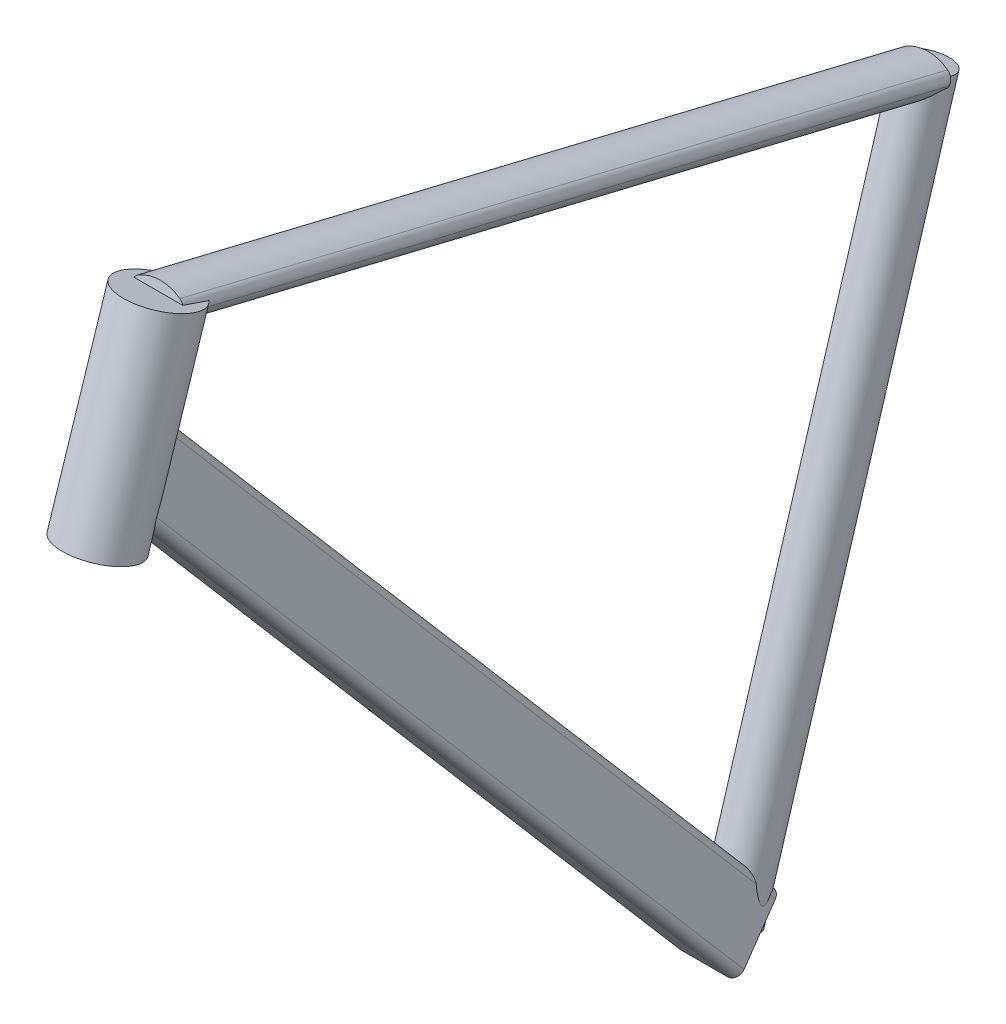
SolidWorks part; units mm, degrees
ref_plane "Plan de face" through (0, 0, 0) normal (0, 0, 1) x (1, 0, 0)
ref_plane "Plan de dessus" through (0, 0, 0) normal (0, 1, 0) x (1, 0, 0)
ref_plane "Plan de droite" through (0, 0, 0) normal (1, 0, 0) x (0, 0, -1)
sketch "Esquisse1" plane through (0, 0, 0) normal (1, 0, 0) x (0, 0, -1)
  line L0 (0, 0) -> (-416.4955, 485.9336)
  line L4 (-416.4955, 485.9336) -> (-390.3242, 566.9614)
  line L5 (-390.3242, 566.9614) -> (132.9546, 440.367)
  line L6 (132.9546, 440.367) -> (0, 0)
  line L7 (-390.3242, 566.9614) -> (220.5054, 566.9614) construction
  line L8 (0, 0) -> (154.0318, 132.0212) construction
  line L9 (-416.4955, 485.9336) -> (-477.5022, 505.6383) construction
  line L10 (0, 0) -> (73.466, -22.1807) construction
  line L11 (-390.3242, 566.9614) -> (-377.98, 617.9864) construction
  point P0 (0, 0)
  dimension "D1" = 13.6
  dimension "D2" = 35.8
  dimension "D3" = 640
  dimension "D4" = 86.8
  dimension "D5" = 94.3
  dimension "D6" = 460
ref_plane "Plan1" through (0, 0, 0) normal (0, 0.7593, 0.6508) x (1, 0, 0)
sketch "Esquisse2" plane through (0, 0, 0) normal (0, 0.7593, 0.6508) x (1, 0, 0)
  line L0 (15, 20.051) -> (21.8, -17.0688)
  line L1 (15.8982, -24.15) -> (-15.8982, -24.15)
  line L2 (-21.8, -17.0688) -> (-15, 20.051)
  line L3 (-10.0818, 24.15) -> (10.0818, 24.15)
  line L4 (0, 0) -> (0, 202.8679) construction
  line L5 (0, 24.15) -> (0, -24.15) construction
  arc A0 (21.8, -17.0688) -> (15.8982, -24.15) centre (15.8982, -18.15) cw
  arc A1 (-15.8982, -24.15) -> (-21.8, -17.0688) centre (-15.8982, -18.15) cw
  arc A2 (15, 20.051) -> (10.0818, 24.15) centre (10.0818, 19.15) ccw
  arc A3 (-15, 20.051) -> (-10.0818, 24.15) centre (-10.0818, 19.15) cw
  point P2 (0, 24.15)
  point P9 (0, -24.15)
  point P21 (0, 0)
  dimension "D2" = 6
  dimension "D4" = 5
  dimension "D1" = 48.3
  dimension "D3" = 43.6
  dimension "D5" = 30
extrude "Boss.-Extru.1" add sketch "Esquisse2" along direction (0, 0.7593, 0.6508) on the side of the normal up to vertex (640 mm away) up to point (0, 485.9336, 416.4955)
ref_plane "Plan2" through (0, 318.2123, -102.7798) normal (0, 0.9516, -0.3074) x (1, 0, 0)
sketch "Esquisse3" plane through (0, 318.2123, -102.7798) normal (0, 0.9516, -0.3074) x (1, 0, 0)
  circle A0 centre (0, -545.6897) radius 25
  dimension "D1" = 50
extrude "Boss.-Extru.2" add sketch "Esquisse3" along normal up to vertex (85.1495 mm away) and the other way blind 50 up to point (0, 566.9614, 390.3242)
ref_plane "Plan3" through (0, 0, 0) normal (0, -0.9573, 0.289) x (-1, 0, 0)
sketch "Esquisse4" plane through (0, 0, 0) normal (0, -0.9573, 0.289) x (-1, 0, 0)
  circle A0 centre (0, 0) radius 16.25
  dimension "D1" = 32.5
extrude "Boss.-Extru.3" add sketch "Esquisse4" against normal up to vertex (460 mm away) up to point (0, 440.367, -132.9546)
sketch "Esquisse5" plane through (0, 15.7162, -18.3364) normal (0, 0.6508, -0.7593) x (-1, 0, 0)
  circle A0 centre (0, 284.7335) radius 2
  circle A1 centre (0, 219.7335) radius 2
  ellipse E0 centre (0, 15.4446) end of major axis (0, -3.8444) minor radius 16.25 (10.0818, 30.5723) -> (-10.0818, 30.5723) ccw construction
  point P11 (0, 34.7335)
  dimension "D3" = 4
  dimension "D1" = 65
  dimension "D2" = 185
ref_plane "Plan4" through (0, 120.5565, 498.3209) normal (0, -0.2351, -0.972) x (-1, 0, 0)
sketch "Esquisse6" plane through (0, 120.5565, 498.3209) normal (0, -0.2351, -0.972) x (-1, 0, 0)
  line L0 (0, 459.2828) -> (0, 511.7797) construction
  line L1 (0, 374.3729) -> (0, 459.2828) construction
  line L2 (-18, 459.2828) -> (18, 459.2828) construction
  arc A0 (-18, 459.2828) -> (18, 459.2828) centre (0, 435.2828) cw
  arc A1 (-18, 459.2828) -> (18, 459.2828) centre (0, 460.863) ccw
  dimension "D1" = 30
  dimension "D2" = 36
extrude "Boss.-Extru.4" add sketch "Esquisse6" along normal up to vertex (538.3743 mm away) up to point (0, 440.367, -132.9546)
fillet "Congé2" radius 6 2 edges at (-18, 503.6642, 128.6848) (18, 503.6642, 128.6848)
